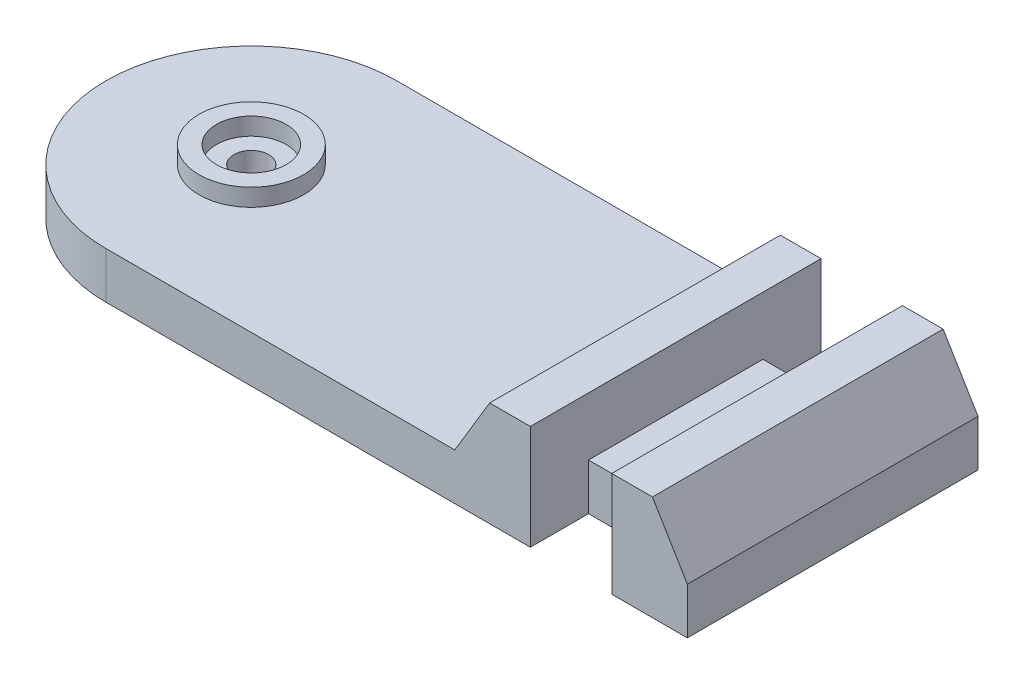
SolidWorks part; units mm, degrees
material "ABS"
ref_plane "前视基准面" through (0, 0, 0) normal (0, 0, 1) x (1, 0, 0)
ref_plane "上视基准面" through (0, 0, 0) normal (0, 1, 0) x (1, 0, 0)
ref_plane "右视基准面" through (0, 0, 0) normal (1, 0, 0) x (0, 0, -1)
sketch "草图1" plane through (0, 0, 0) normal (0, 1, 0) x (1, 0, 0)
  line L0 (0, 12.5) -> (50, 12.5)
  line L1 (50, 12.5) -> (50, -12.5)
  line L2 (50, -12.5) -> (0, -12.5)
  line L3 (-17.9664, 0) -> (77.456, 0) construction
  circle A0 centre (0, 0) radius 12.5
  circle A1 centre (0, 0) radius 1.5
  circle A2 centre (40, 0) radius 1.5
  dimension "D1" = 25
  dimension "D3" = 3
  dimension "D4" = 3
  dimension "D2" = 50
  dimension "D5" = 40
extrude "凸台-拉伸1" add sketch "草图1" along normal blind 4 contours A0 L3 A1 | L3 A0 A1 | A0 L3 A2 L1 L0 | L3 A0 L2 L1 A2 region at (29.7397, 0, -6.5223) region at (0, 0, -5.3734) region at (0, 0, 5.3734) region at (29.7397, 0, 6.5223)
sketch "草图2" plane through (0, 4, 0) normal (0, 1, 0) x (1, 0, 0)
  circle A0 centre (0, 0) radius 3
  circle A1 centre (0, 0) radius 4.5
  dimension "D1" = 6
  dimension "D2" = 9
extrude "凸台-拉伸2" add sketch "草图2" along normal blind 1.5
sketch "草图3" plane through (0, 0, 12.5) normal (0, 0, 1) x (1, 0, 0)
  line L0 (40, 13.5103) -> (40, -9.5748) construction
  line L1 (33, 9) -> (47, 9)
  line L2 (47, 9) -> (50, 4)
  line L3 (50, 4) -> (30, 4)
  line L4 (50, 4) -> (0, 4) construction
  line L5 (33, 9) -> (30, 4)
  point P11 (40, 4)
  point P12 (40, 9)
  dimension "D1" = 40
  dimension "D2" = 7
  dimension "D3" = 5
extrude "凸台-拉伸3" add sketch "草图3" against normal up to surface (25 mm away) up to face at (25, 2, -12.5)
sketch "草图4" plane through (0, 0, 12.5) normal (0, 0, 1) x (1, 0, 0)
  line L0 (40, 14.712) -> (40, -12.897) construction
  line L1 (36.5, 9) -> (43.5, 9)
  line L2 (47, 9) -> (33, 9) construction
  line L3 (43.5, 9) -> (43.5, 4)
  line L4 (43.5, 4) -> (36.5, 4)
  line L5 (36.5, 9) -> (36.5, 4)
  point P10 (40, 4)
  point P11 (40, 9)
  dimension "D1" = 40
  dimension "D2" = 3.5
  dimension "D3" = 5
extrude "切除-拉伸1" cut sketch "草图4" against normal through all
sketch "草图5" plane through (0, 4, 0) normal (0, 1, 0) x (1, 0, 0)
  line L0 (-19.9448, 0) -> (64.5272, 0) construction
  line L1 (36.5, -12.5) -> (43.5, -12.5)
  line L2 (43.5, -12.5) -> (43.5, -7.5)
  line L3 (43.5, 12.5) -> (43.5, -12.5) construction
  line L4 (43.5, -7.5) -> (36.5, -7.5)
  line L5 (36.5, 12.5) -> (36.5, -12.5) construction
  line L6 (36.5, -7.5) -> (36.5, -12.5)
  line L7 (36.5, 7.5) -> (36.5, 12.5)
  line L8 (36.5, 12.5) -> (43.5, 12.5)
  line L9 (43.5, 12.5) -> (43.5, 7.5)
  line L10 (43.5, 7.5) -> (36.5, 7.5)
  dimension "D1" = 5
extrude "切除-拉伸2" cut sketch "草图5" against normal through all
